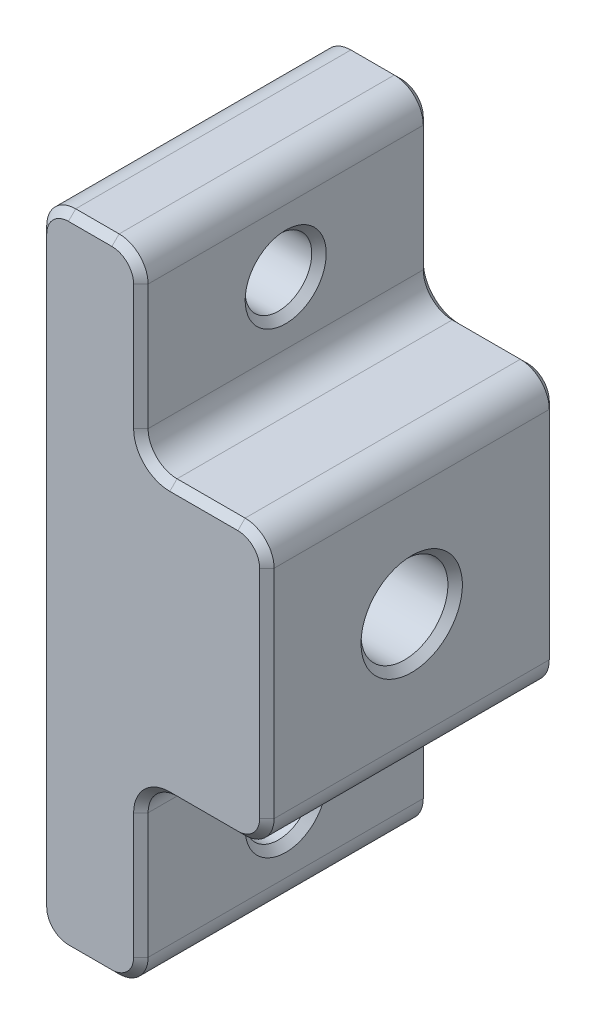
SolidWorks part; units mm, degrees
ref_plane "Front" through (0, 0, 0) normal (0, 0, 1) x (1, 0, 0)
ref_plane "Top" through (0, 0, 0) normal (0, 1, 0) x (1, 0, 0)
ref_plane "Right" through (0, 0, 0) normal (1, 0, 0) x (0, 0, -1)
sketch "Skizze1" plane through (0, 0, 0) normal (0, 0, 1) x (1, 0, 0)
  line L0 (0, 0) -> (19.3854, 0) construction
  line L1 (0, -22.1303) -> (0, 22.1303)
  line L2 (0, 22.1303) -> (7, 22.1303)
  line L3 (7, 22.1303) -> (7, 9.4858)
  line L4 (7, 9.4858) -> (15.7, 9.4858)
  line L5 (15.7, 9.4858) -> (15.7, -9.4858)
  line L6 (7, -9.4858) -> (15.7, -9.4858)
  line L7 (7, -22.1303) -> (7, -9.4858)
  line L8 (0, -22.1303) -> (7, -22.1303)
  point P9 (15.7, 0)
  dimension "D1" = 7
  dimension "D2" = 15.7
extrude "Aufsatz-Linear austragen1" add sketch "Skizze1" along normal blind 20
sketch "Skizze2" plane through (15.7, 0, 0) normal (1, 0, 0) x (0, 0, -1)
  line L0 (0, 0) -> (-20, 0) construction
  line L1 (-20, -9.4858) -> (-20, 9.4858) construction
  circle A0 centre (-10, 0) radius 3
  dimension "D1" = 6
extrude "Schnitt-Linear austragen1" cut sketch "Skizze2" against normal blind 20
sketch "Skizze3" plane through (0, 0, 0) normal (-1, 0, 0) x (0, 0, 1)
  circle A0 centre (10, 0) radius 5.25
  dimension "D1" = 10.5
extrude "Schnitt-Linear austragen2" cut sketch "Skizze3" against normal offset from surface (6.2 mm away) 9.5 up to face at (15.7, 0, 7)
sketch "Skizze4" plane through (7, 0, 0) normal (1, 0, 0) x (0, 0, -1)
  line L0 (-10, -9.4858) -> (-10, -22.1303) construction
  line L1 (-20, -9.4858) -> (0, -9.4858) construction
  line L2 (-20, -22.1303) -> (0, -22.1303) construction
  line L3 (0, 0) -> (-20, 0) construction
  line L4 (-20, -9.4858) -> (-20, 9.4858) construction
  circle A0 centre (-10, -15.8081) radius 2.3
  circle A1 centre (-10, 15.8081) radius 2.3
  dimension "D1" = 4.6
extrude "Schnitt-Linear austragen3" cut sketch "Skizze4" against normal blind 10
fillet "Verrundung1" radius 2 8 edges at (0, 22.1303, 10) (7, -9.4858, 10) (7, 22.1303, 10) (7, 9.4858, 10) (15.7, 9.4858, 10) (15.7, -9.4858, 10) (7, -22.1303, 10) (0, -22.1303, 10)
chamfer "Fase1" distance 0.5 angle 45 39 edges at (0, 15.8081, 7.7) (7, 15.8081, 12.3) (6.2, 0, 13) (15.7, 0, 7) (0, -15.8081, 7.7) (7, -15.8081, 7.7) (7, -15.8081, 20) (3.5, -22.1303, 20) (0, 0, 20) (3.5, 22.1303, 20) (7, 15.8081, 20) (11.35, 9.4858, 20) (15.7, 0, 20) (11.35, -9.4858, 20) (15.7, 0, 0) (11.35, 9.4858, 0) (7, 15.8081, 0) (3.5, 22.1303, 0) (0, 0, 0) (3.5, -22.1303, 0) (7, -15.8081, 0) (11.35, -9.4858, 0) (0, 0, 15.25) (6.4142, 21.5445, 20) (7.5858, 10.0716, 20) (15.1142, 8.9, 20) (15.1142, -8.9, 20) (7.5858, -10.0716, 20) (6.4142, -21.5445, 20) (0.5858, -21.5445, 20) (0.5858, 21.5445, 20) (0.5858, -21.5445, 0) (6.4142, -21.5445, 0) (7.5858, -10.0716, 0) (15.1142, -8.9, 0) (15.1142, 8.9, 0) (7.5858, 10.0716, 0) (6.4142, 21.5445, 0) (0.5858, 21.5445, 0)
